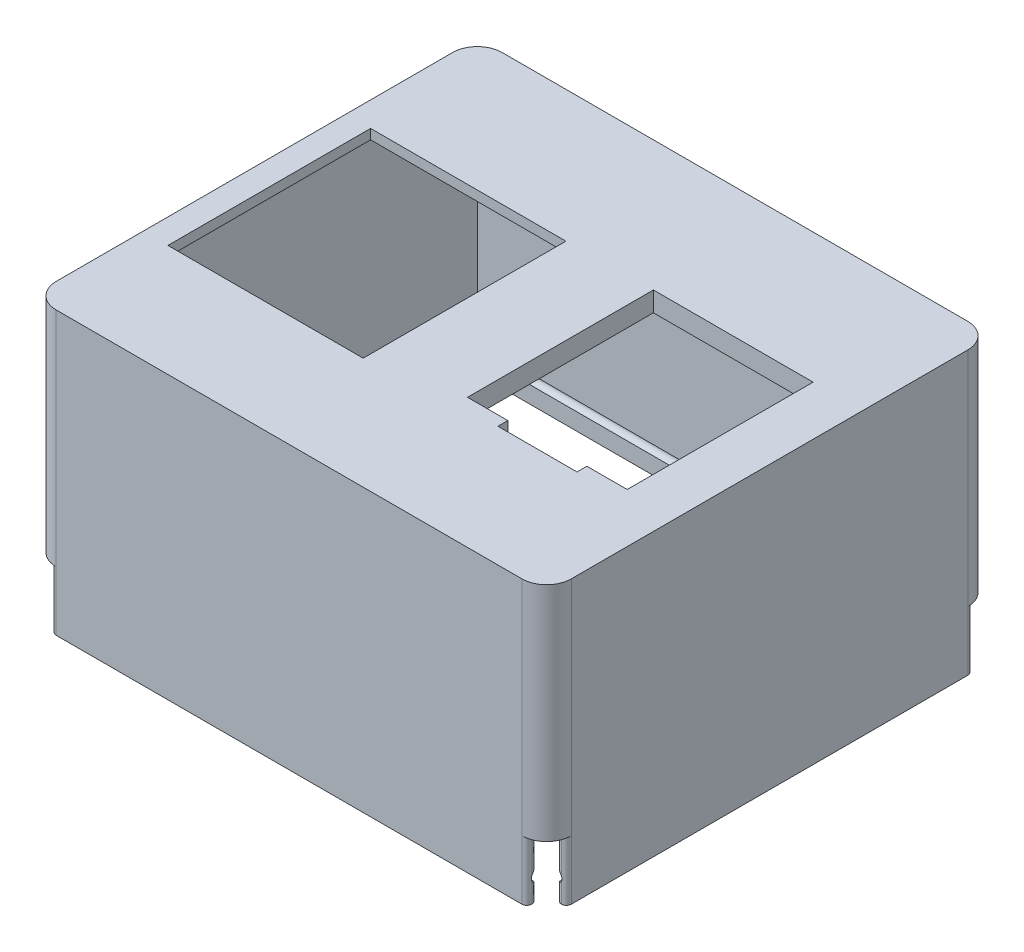
SolidWorks part; units mm, degrees
ref_plane "Plan de face" through (0, 0, 0) normal (0, 0, 1) x (1, 0, 0)
ref_plane "Plan de dessus" through (0, 0, 0) normal (0, 1, 0) x (1, 0, 0)
ref_plane "Plan de droite" through (0, 0, 0) normal (1, 0, 0) x (0, 0, -1)
sketch "Esquisse1" plane through (0, 0, 0) normal (0, 1, 0) x (1, 0, 0)
  line L1 (-52.1, -45.1) -> (52.1, -45.1)
  line L2 (-52.1, -45.1) -> (-52.1, 45.1)
  line L3 (-52.1, 45.1) -> (52.1, 45.1)
  line L4 (52.1, -45.1) -> (52.1, 45.1)
  line L5 (-52.1, -45.1) -> (52.1, 45.1) construction
  line L6 (-52.1, 45.1) -> (52.1, -45.1) construction
  point P0 (0, 0)
  dimension "D1" = 104.2
  dimension "D2" = 90.2
extrude "Boss.-Extru.1" add sketch "Esquisse1" along normal blind 2
sketch "Esquisse2" plane through (0, 0, 0) normal (0, -1, 0) x (1, 0, 0)
  line L8 (50.1, -43.1) -> (50.1, 43.1)
  line L9 (50.1, 43.1) -> (-50.1, 43.1)
  line L10 (-50.1, 43.1) -> (-50.1, -43.1)
  line L11 (-50.1, -43.1) -> (50.1, -43.1)
  line L12 (50.1, -43.1) -> (50.1, 43.1)
  line L13 (50.1, 43.1) -> (-50.1, 43.1)
  line L14 (-50.1, 43.1) -> (-50.1, -43.1)
  line L15 (-50.1, -43.1) -> (50.1, -43.1)
  line L16 (52.1, -45.1) -> (52.1, 45.1)
  line L17 (52.1, 45.1) -> (-52.1, 45.1)
  line L18 (-52.1, 45.1) -> (-52.1, -45.1)
  line L19 (-52.1, -45.1) -> (52.1, -45.1)
  line L20 (52.1, -45.1) -> (52.1, 45.1)
  line L21 (52.1, 45.1) -> (-52.1, 45.1)
  line L22 (-52.1, 45.1) -> (-52.1, -45.1)
  line L23 (-52.1, -45.1) -> (52.1, -45.1)
  dimension "D1" = 2
  dimension "D2" = 0
extrude "Boss.-Extru.2" add sketch "Esquisse2" along normal blind 55
sketch "Esquisse3" plane through (0, -55, 0) normal (0, -1, 0) x (1, 0, 0)
  line L0 (-50.1, 41.1) -> (-50.1, 43.1)
  line L1 (-52.1, 45.1) -> (-48.1, 45.1)
  line L2 (-52.1, 45.1) -> (-52.1, 41.1)
  line L3 (-52.1, 41.1) -> (-50.1, 41.1)
  line L4 (-48.1, 45.1) -> (-48.1, 43.1)
  line L5 (-50.1, 43.1) -> (-48.1, 43.1)
  dimension "D1" = 4
  dimension "D2" = 4
  dimension "D3" = 2
  dimension "D4" = 2
extrude "Enlèv. mat.-Extru.1" cut sketch "Esquisse3" against normal blind 12
mirror "Symétrie1" about plane through (0, 0, 0) normal (0, 0, 1) of "Enlèv. mat.-Extru.1"
mirror "Symétrie2" about plane through (0, 0, 0) normal (1, 0, 0) of "Symétrie1"
fillet "Congé3" radius 1 16 edges at (-48.1, -49, 45.1) (-48.1, -49, 43.1) (-50.1, -49, 41.1) (-52.1, -49, 41.1) (48.1, -49, 45.1) (48.1, -49, 43.1) (52.1, -49, 41.1) (50.1, -49, 41.1) (52.1, -49, -41.1) (50.1, -49, -41.1) (48.1, -49, -43.1) (48.1, -49, -45.1) (-48.1, -49, -45.1) (-48.1, -49, -43.1) (-50.1, -49, -41.1) (-52.1, -49, -41.1)
fillet "Congé1" radius 5 4 edges at (52.1, -20.5, 45.1) (52.1, -20.5, -45.1) (-52.1, -20.5, -45.1) (-52.1, -20.5, 45.1)
sketch "Esquisse4" plane through (0, 0, 0) normal (1, 0, 0) x (0, 0, -1)
  line L0 (-43.1, -43) -> (-43.1, -55) construction
  line L1 (-43.1, -49.4) -> (-43.1, -51.6)
  line L2 (-44.1, -55) -> (-43.1, -55) construction
  arc A1 (-43.1, -49.4) -> (-43.1, -51.6) centre (-43.1, -50.5) ccw
  dimension "D1" = 1.1
  dimension "D2" = 4.5
extrude "Enlèv. mat.-Extru.2" cut sketch "Esquisse4" against normal through all both and the other way through all
mirror "Symétrie4" about plane through (0, 0, 0) normal (0, 0, 1) of "Enlèv. mat.-Extru.2"
sketch "Esquisse5" plane through (0, 0, 0) normal (0, 0, 1) x (1, 0, 0)
  line L0 (-50.1, -43) -> (-50.1, -55) construction
  line L1 (-51.1, -55) -> (-50.1, -55) construction
  line L2 (-50.1, -49.4) -> (-50.1, -51.6)
  arc A0 (-50.1, -49.4) -> (-50.1, -51.6) centre (-50.1, -50.5) ccw
  dimension "D1" = 1.1
  dimension "D2" = 4.5
extrude "Enlèv. mat.-Extru.3" cut sketch "Esquisse5" against normal through all both and the other way through all
mirror "Symétrie5" about plane through (0, 0, 0) normal (1, 0, 0) of "Enlèv. mat.-Extru.3"
sketch "Esquisse6" plane through (-52.1, 0, 0) normal (-1, 0, 0) x (0, 0, 1)
  line L0 (0, 15.9382) -> (0, -19.3286) construction
  line L1 (-40.1, 2) -> (40.1, 2) construction
  line L2 (-10.15, -14) -> (10.15, -14)
  line L3 (-10.15, -14) -> (-10.15, 0)
  line L4 (-10.15, 0) -> (10.15, 0)
  line L5 (10.15, -14) -> (10.15, 0)
  line L6 (-10.15, -14) -> (10.15, 0) construction
  line L7 (-10.15, 0) -> (10.15, -14) construction
  point P3 (0, -7)
  dimension "D1" = 14
  dimension "D2" = 2
  dimension "D3" = 20.3
extrude "Enlèv. mat.-Extru.4" [suppressed] cut sketch "Esquisse6" against normal blind 5 and the other way through all
sketch "Esquisse7" plane through (-52.1, 0, 0) normal (-1, 0, 0) x (0, 0, 1)
  line L0 (0, 0) -> (0, 2) construction
  line L1 (-40.1, 2) -> (40.1, 2) construction
  line L3 (-8.1, 0) -> (8.1, 0)
  line L4 (-8.1, 0) -> (-8.1, 2)
  line L5 (-8.1, 2) -> (8.1, 2)
  line L6 (8.1, 0) -> (8.1, 2)
  line L7 (-8.1, 0) -> (8.1, 2) construction
  line L8 (-8.1, 2) -> (8.1, 0) construction
  point P7 (0, 1)
  dimension "D1" = 16.2
extrude "Enlèv. mat.-Extru.5" [suppressed] cut sketch "Esquisse7" against normal blind 18.3
sketch "Esquisse8" plane through (0, 2, 0) normal (0, 1, 0) x (1, 0, 0)
  line L0 (0, 0) -> (52.1, 0) construction
  line L1 (52.1, -40.1) -> (52.1, 40.1) construction
  line L3 (9.8, -18.8) -> (42.1, -18.8)
  line L4 (9.8, -18.8) -> (9.8, 18.8)
  line L5 (9.8, 18.8) -> (42.1, 18.8)
  line L6 (42.1, -18.8) -> (42.1, 18.8)
  line L7 (9.8, -18.8) -> (42.1, 18.8) construction
  line L8 (9.8, 18.8) -> (42.1, -18.8) construction
  point P5 (25.95, 0)
  dimension "D1" = 32.3
  dimension "D2" = 37.6
  dimension "D3" = 10
extrude "Enlèv. mat.-Extru.6" cut sketch "Esquisse8" against normal blind 3
sketch "Esquisse9" plane through (0, 0, 0) normal (0, -1, 0) x (1, 0, 0)
  line L0 (9.8, 18.8) -> (9.8, -18.8) construction
  line L1 (3.8, -24.8) -> (48.1, -24.8)
  line L2 (3.8, -24.8) -> (3.8, 24.8)
  line L3 (3.8, 24.8) -> (48.1, 24.8)
  line L4 (48.1, -24.8) -> (48.1, 24.8)
  line L5 (3.8, -24.8) -> (48.1, 24.8) construction
  line L6 (3.8, 24.8) -> (48.1, -24.8) construction
  line L7 (42.1, 18.8) -> (9.8, 18.8) construction
  line L8 (42.1, -18.8) -> (42.1, 18.8) construction
  line L9 (9.8, -18.8) -> (42.1, -18.8) construction
  line L10 (42.1, 18.8) -> (9.8, 18.8)
  line L11 (42.1, -18.8) -> (42.1, 18.8)
  line L12 (9.8, -18.8) -> (42.1, -18.8)
  line L13 (9.8, 18.8) -> (9.8, -18.8)
  point P0 (25.95, 0)
  dimension "D1" = 6
  dimension "D2" = 6
  dimension "D3" = 6
  dimension "D4" = 6
extrude "Boss.-Extru.3" add sketch "Esquisse9" along normal blind 2
sketch "Esquisse10" plane through (0, 2, 0) normal (0, 1, 0) x (1, 0, 0)
  line L0 (25.95, 18.8) -> (25.95, -18.8) construction
  line L1 (42.1, 18.8) -> (9.8, 18.8) construction
  line L2 (9.8, -18.8) -> (42.1, -18.8) construction
  line L4 (17.95, -18.8) -> (33.95, -18.8)
  line L5 (17.95, -18.8) -> (17.95, -20.8)
  line L6 (17.95, -20.8) -> (33.95, -20.8)
  line L7 (33.95, -18.8) -> (33.95, -20.8)
  dimension "D1" = 2
  dimension "D2" = 16
extrude "Enlèv. mat.-Extru.7" cut sketch "Esquisse10" against normal through all
sketch "Esquisse11" [suppressed] plane through (0, 0, 0) normal (0, 1, 0) x (1, 0, 0)
  line L0 (-52.1, 0) -> (-32.1, 0) construction
  line L1 (-52.1, 10.15) -> (-52.1, -10.15) construction
  line L3 (-52.1, 40.1) -> (-52.1, 8.1) construction
  line L4 (-52.1, -10.15) -> (-32.1, -10.15)
  line L5 (-52.1, -10.15) -> (-52.1, 10.15)
  line L6 (-52.1, 10.15) -> (-32.1, 10.15)
  line L7 (-32.1, -10.15) -> (-32.1, 10.15)
  line L8 (-52.1, -10.15) -> (-32.1, 10.15) construction
  line L9 (-52.1, 10.15) -> (-32.1, -10.15) construction
  point P6 (-42.1, 0)
  dimension "D1" = 20.3
  dimension "D2" = 20
extrude "Enlèv. mat.-Extru.8" [suppressed] cut sketch "Esquisse11" along normal blind 0.4
sketch "Esquisse13" plane through (0, -2, 0) normal (0, -1, 0) x (1, 0, 0)
  line L0 (42.1, -18.8) -> (42.1, 18.8) construction
  line L1 (9.8, 18.8) -> (9.8, -18.8) construction
  line L2 (9.8, -18.8) -> (42.1, -18.8) construction
  circle A0 centre (45.3, -10.8) radius 0.75
  circle A1 centre (5.2, 9.2) radius 0.75
  circle A2 centre (15.6, -21.4) radius 0.75
  dimension "D5" = 1.5
  dimension "D6" = 1.5
  dimension "D9" = 1.5
  dimension "D1" = 3.2
  dimension "D2" = 4.6
  dimension "D3" = 8
  dimension "D4" = 28
  dimension "D7" = 2.6
  dimension "D8" = 5.8
extrude "Enlèv. mat.-Extru.9" cut sketch "Esquisse13" against normal blind 3
sketch "Esquisse14" plane through (0, -2, 0) normal (0, -1, 0) x (1, 0, 0)
  line L0 (3.8, 11.3909) -> (3.8, 7.0091)
  line L1 (3.8, 24.8) -> (3.8, -24.8) construction
  line L2 (3.8, 24.8) -> (3.8, -24.8) construction
  arc A0 (3.8, 11.3909) -> (3.8, 7.0091) centre (5.2, 9.2) ccw
  dimension "D1" = 5.2
extrude "Boss.-Extru.4" add sketch "Esquisse14" against normal up to surface (2 mm away) up to face at (0, 0, 0)
sketch "Esquisse15" plane through (0, -55, 0) normal (0, -1, 0) x (1, 0, 0)
  line L0 (-50.1, 40.1) -> (-50.1, -40.1) construction
  line L1 (50.3, -43.3) -> (-50.3, -43.3)
  line L2 (50.3, -43.3) -> (50.3, 43.3)
  line L3 (50.3, 43.3) -> (-50.3, 43.3)
  line L4 (-50.3, -43.3) -> (-50.3, 43.3)
  line L5 (50.3, -43.3) -> (-50.3, 43.3) construction
  line L6 (50.3, 43.3) -> (-50.3, -43.3) construction
  line L7 (47.1, 43.1) -> (-47.1, 43.1) construction
  point P0 (0, 0)
  dimension "D1" = 0.2
  dimension "D2" = 0.2
extrude "Enlèv. mat.-Extru.10" cut sketch "Esquisse15" against normal blind 4.5
sketch "Esquisse16" plane through (-52.1, 0, 0) normal (-1, 0, 0) x (0, 0, 1)
  circle A0 centre (-13, -7) radius 1.5
  dimension "D1" = 3
extrude "Enlèv. mat.-Extru.11" [suppressed] cut sketch "Esquisse16" against normal blind 4
mirror "Symétrie6" [suppressed] about plane through (0, 0, 0) normal (0, 0, 1)
sketch "Esquisse17" plane through (0, 0, 0) normal (0, -1, 0) x (1, 0, 0)
  line L0 (-50.1, 0) -> (0, 0) construction
  line L1 (-50.1, 43.1) -> (-50.1, -43.1) construction
  line L2 (-50.1, 40.1) -> (-50.1, 43.1) construction
  line L3 (-47.1, -18.5) -> (-7.6, -18.5)
  line L4 (-47.1, -18.5) -> (-47.1, 22.5)
  line L5 (-47.1, 22.5) -> (-7.6, 22.5)
  line L6 (-7.6, -18.5) -> (-7.6, 22.5)
  line L7 (-47.1, -18.5) -> (-7.6, 22.5) construction
  line L8 (-47.1, 22.5) -> (-7.6, -18.5) construction
  point P5 (-27.35, 2)
  dimension "D1" = 39.5
  dimension "D2" = 41
  dimension "D3" = 3
  dimension "D4" = 2
extrude "Enlèv. mat.-Extru.12" cut sketch "Esquisse17" against normal up to next
sketch "Esquisse19" plane through (0, 0, 0) normal (0, -1, 0) x (1, 0, 0)
  line L0 (-47.1, 22.5) -> (-47.1, -18.5) construction
  line L1 (-44.1, 32.5) -> (-12.3, 32.5) construction
  line L2 (-44.1, 32.5) -> (-44.1, -39) construction
  line L3 (-44.1, -39) -> (-12.3, -39) construction
  line L4 (-12.3, 32.5) -> (-12.3, -39) construction
  line L6 (-47.1, -18.5) -> (-7.6, -18.5) construction
  circle A0 centre (-44.1, 32.5) radius 4
  circle A1 centre (-44.1, -39) radius 4
  circle A2 centre (-12.3, 32.5) radius 4
  circle A3 centre (-12.3, -39) radius 4
  dimension "D5" = 8
  dimension "D6" = 8
  dimension "D7" = 8
  dimension "D8" = 8
  dimension "D1" = 3
  dimension "D2" = 31.8
  dimension "D3" = 71.5
  dimension "D4" = 20.5
extrude "Boss.-Extru.5" add sketch "Esquisse19" along normal blind 9
sketch "Esquisse20" plane through (0, -9, 0) normal (0, -1, 0) x (1, 0, 0)
  circle A0 centre (-44.1, 32.5) radius 2.05
  dimension "D1" = 4.1
extrude "Enlèv. mat.-Extru.13" cut sketch "Esquisse20" against normal blind 10
pattern_linear "Répétition linéaire1" count 2 spacing 31.8 along (1, 0, 0) count 2 spacing 71.5 along (0, 0, -1) of "Enlèv. mat.-Extru.13"
sketch "Esquisse21" plane through (0, 2, 0) normal (0, 1, 0) x (1, 0, 0)
  line L1 (-50.0193, 44.4136) -> (-2.2418, 44.4136)
  line L2 (-50.0193, 44.4136) -> (-50.0193, -40.4592)
  line L3 (-50.0193, -40.4592) -> (-2.2418, -40.4592)
  line L4 (-2.2418, 44.4136) -> (-2.2418, -40.4592)
  line L5 (-61.088, 55.0958) -> (60.8078, 55.0958)
  line L6 (-61.088, 55.0958) -> (-61.088, -50.267)
  line L7 (-61.088, -50.267) -> (60.8078, -50.267)
  line L8 (60.8078, 55.0958) -> (60.8078, -50.267)
extrude "Enlèv. mat.-Extru.14" [suppressed] cut sketch "Esquisse21" against normal through all
sketch "Esquisse22" [suppressed] plane through (0, 0, -44.4136) normal (0, 0, -1) x (-1, 0, 0)
  line L1 (-3.5624, -9.8336) -> (56.1199, -9.8336)
  line L2 (-3.5624, -9.8336) -> (-3.5624, -57.8347)
  line L3 (-3.5624, -57.8347) -> (56.1199, -57.8347)
  line L4 (56.1199, -9.8336) -> (56.1199, -57.8347)
extrude "Enlèv. mat.-Extru.15" [suppressed] cut sketch "Esquisse22" against normal through all
equation "\"D6@Esquisse19\"=\"D5@Esquisse19\""
equation "\"D7@Esquisse19\"=\"D5@Esquisse19\""
equation "\"D8@Esquisse19\"=\"D5@Esquisse19\""
